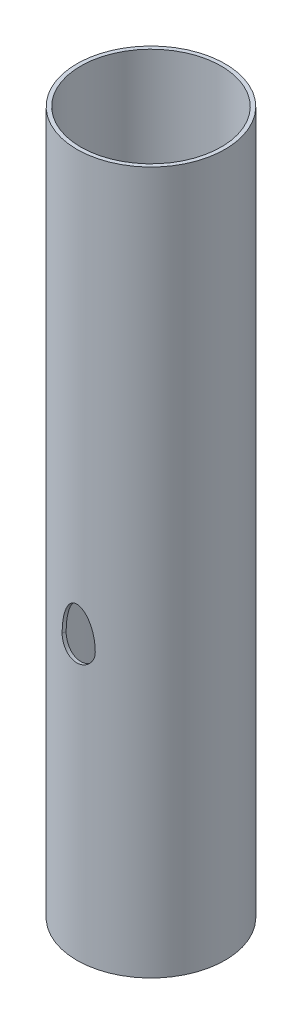
SolidWorks part; units mm, degrees
ref_plane "Front Plane" through (0, 0, 0) normal (0, 0, 1) x (1, 0, 0)
ref_plane "Top Plane" through (0, 0, 0) normal (0, 1, 0) x (1, 0, 0)
ref_plane "Right Plane" through (0, 0, 0) normal (1, 0, 0) x (0, 0, -1)
sketch "Sketch2" plane through (0, 0, 0) normal (0, 1, 0) x (1, 0, 0)
  circle A0 centre (0, 0) radius 36
  circle A1 centre (0, 0) radius 38
  dimension "D1" = 2
  dimension "D2" = 76
extrude "Boss-Extrude1" add sketch "Sketch2" along normal blind 360
ref_axis "Axis1" through (41.8, 0, 0) along (-1, 0, 0)
ref_plane "Plane1" through (0, 0, 0) normal (0, 0.2045, 0.9789) x (-1, 0, 0)
sketch "Sketch3" plane through (0, 0, 0) normal (0, 0.2045, 0.9789) x (-1, 0, 0)
  line L0 (0, 41.8) -> (0, -41.8) construction
  line L2 (-41.8, 0) -> (41.8, 0) construction
  arc A0 (8.5, -130) -> (-8.5, -130) centre (0, -130) ccw
  arc A1 (-8.5, -130) -> (8.5, -130) centre (0, -130) ccw construction
  ellipse E0 centre (0, -130) end of major axis (0, -147) minor radius 8.5 (-8.5, -130) -> (8.5, -130) ccw
  dimension "D1" = 17
  dimension "D2" = 130
  dimension "D3" = 17
extrude "Cut-Extrude1" cut sketch "Sketch3" along normal up to next
